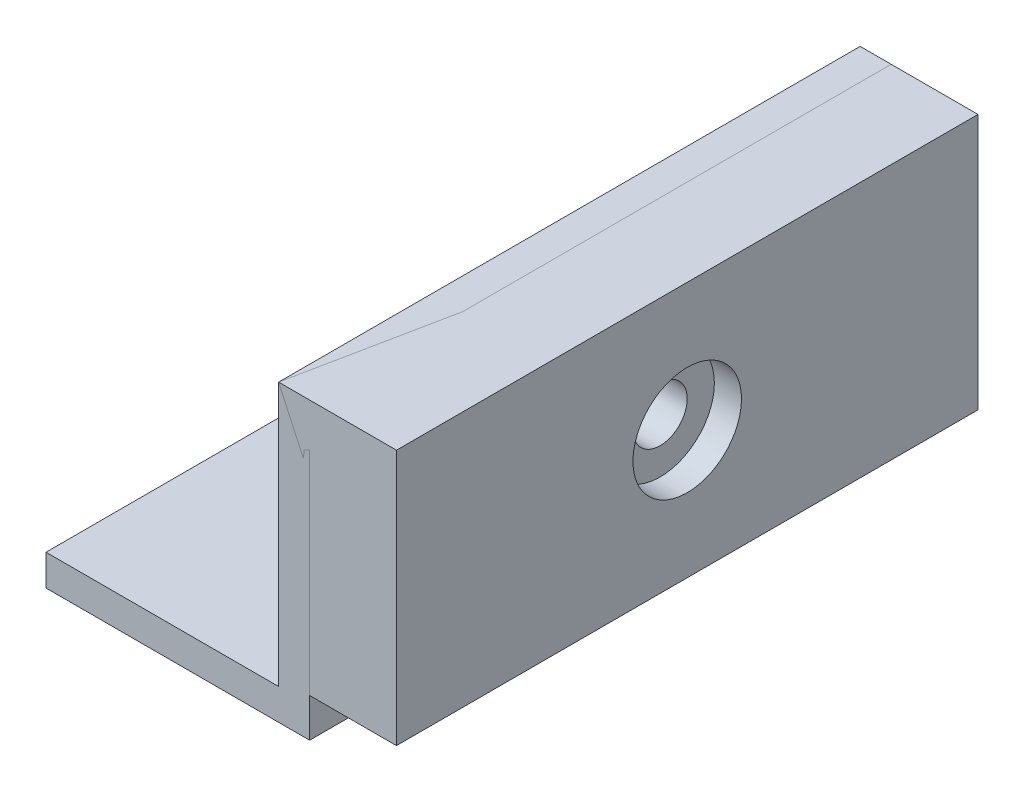
SolidWorks part; units mm, degrees
material "AISI 1020 Steel, Cold Rolled"
ref_plane "Front Plane" through (0, 0, 0) normal (0, 0, 1) x (1, 0, 0)
ref_plane "Top Plane" through (0, 0, 0) normal (0, 1, 0) x (1, 0, 0)
ref_plane "Right Plane" through (0, 0, 0) normal (1, 0, 0) x (0, 0, -1)
sketch "Sketch1" plane through (0, 0, 0) normal (1, 0, 0) x (0, 0, -1)
  line L1 (-37.5, 16.5) -> (37.5, 16.5)
  line L2 (-37.5, 16.5) -> (-37.5, -16.5)
  line L3 (-37.5, -16.5) -> (37.5, -16.5)
  line L4 (37.5, 16.5) -> (37.5, -16.5)
  line L5 (0, -16.5) -> (0, 16.5) construction
  line L6 (-37.5, 0) -> (37.5, 0) construction
  circle A0 centre (0, 0) radius 3.5
  point P0 (0, 0)
  dimension "D3" = 7
  dimension "D1" = 75
  dimension "D2" = 33
extrude "Boss-Extrude1" add sketch "Sketch1" along normal blind 11.2
sketch "Sketch2" plane through (11.2, 0, 0) normal (1, 0, 0) x (0, 0, -1)
  circle A0 centre (0, 0) radius 7
  dimension "D1" = 14
extrude "Cut-Extrude1" cut sketch "Sketch2" against normal blind 3.5
sketch "Sketch3" plane through (0, 0, 0) normal (-1, 0, 0) x (0, 0, 1)
  line L0 (-37.5, 16.5) -> (37.5, 16.5) construction
  line L1 (0, -16.5) -> (-37.5, -16.5) construction
  line L2 (37.5, -16.5) -> (37.5, 16.5)
  line L3 (37.5, 16.5) -> (-37.5, 16.5)
  line L4 (-37.5, -16.5) -> (-37.5, 16.5)
  line L5 (0, 16.5) -> (0, -16.5) construction
  line L6 (37.5, 0) -> (-37.5, 0) construction
  line L8 (37.5, 16.5) -> (-37.5, 16.5)
  line L12 (0, -16.5) -> (-37.5, -16.5) construction
  line L13 (37.5, -16.5) -> (37.5, -21.5)
  line L14 (37.5, -21.5) -> (-37.5, -21.5)
  line L15 (-37.5, -16.5) -> (-37.5, -21.5)
  line L16 (37.5, -21.5) -> (-37.5, -21.5)
  line L17 (37.5, -21.5) -> (37.5, 16.5)
  line L18 (37.5, 16.5) -> (-37.5, 16.5)
  line L19 (-37.5, -21.5) -> (-37.5, 16.5)
  circle A0 centre (0, 0) radius 3.5
  point P0 (0, 0)
  line M6 (-37.5, -16.5) -> (37.5, -16.5)
  line M8 (37.5, 16.5) -> (-37.5, 16.5)
  circle M9 centre (0, 0) radius 3.5
  dimension "D1" = 75
  dimension "D2" = 5
extrude "Boss-Extrude2" add sketch "Sketch3" along normal blind 4 contours L4 L2 M6 M8 M9 | M8 region at (0, -15.6806, 0)
extrude "Boss-Extrude4" add sketch "Sketch3<3>" along normal blind 4 separate body contours L4 L2 M6 M8 M9 | L15 L14 L13 M6 region at (0, -15.6806, 0) region at (0, -19, 0)
sketch "Sketch3<3>" plane through (0, 0, 0) normal (-1, 0, 0) x (0, 0, 1) same geometry as "Sketch3"
sketch "Sketch6" plane through (-4, 0, 0) normal (-1, 0, 0) x (0, 0, 1)
  line L0 (-37.5, 16.5) -> (-37.5, -21.5) construction
  line L1 (37.5, -21.5) -> (-37.5, -21.5)
  line L2 (37.5, -21.5) -> (37.5, -17.498)
  line L3 (37.5, -17.498) -> (-37.5, -17.498)
  line L4 (-37.5, -21.5) -> (-37.5, -17.498)
  dimension "D1" = 4.002
extrude "Boss-Extrude6" add sketch "Sketch6" along normal blind 30
